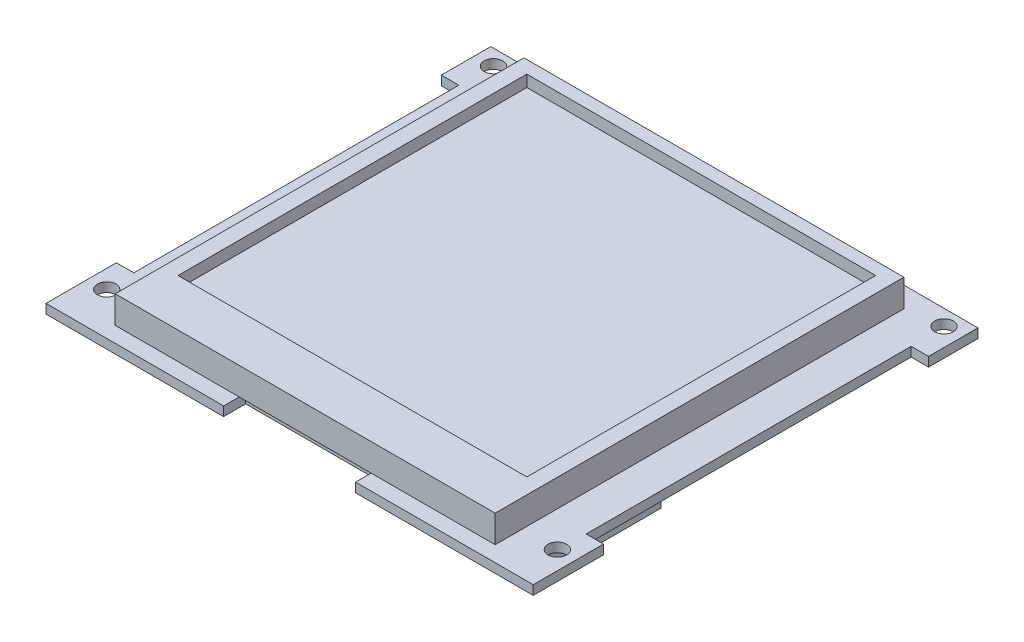
SolidWorks part; units mm, degrees
other "PCB"
other "显示屏"
ref_plane "前视基准面" through (0, 0, 0) normal (0, 0, 1) x (1, 0, 0)
ref_plane "上视基准面" through (0, 0, 0) normal (0, 1, 0) x (1, 0, 0)
ref_plane "右视基准面" through (0, 0, 0) normal (1, 0, 0) x (0, 0, -1)
other "Configuration Table"
sketch "草图1" plane through (0, 0, 0) normal (0, 1, 0) x (1, 0, 0)
  line L1 (-30, 70.8) -> (30, 70.8)
  line L2 (-30, 70.8) -> (-30, 10.8)
  line L3 (-30, 10.8) -> (30, 10.8)
  line L4 (30, 70.8) -> (30, 10.8)
  line L5 (-32.675, 72.98) -> (32.675, 72.98)
  line L6 (-32.675, 72.98) -> (-32.675, 2.68)
  line L7 (-32.675, 2.68) -> (32.675, 2.68)
  line L8 (32.675, 72.98) -> (32.675, 2.68)
  line L9 (-38.75, 73.8) -> (38.75, 73.8) construction
  line L10 (-38.75, 73.8) -> (-38.75, 7.3) construction
  line L11 (-38.75, 7.3) -> (38.75, 7.3) construction
  line L12 (38.75, 73.8) -> (38.75, 7.3) construction
  line L28 (-41.9, 76.5) -> (-41.9, 68)
  line L29 (-41.9, 68) -> (-38.9, 68)
  line L30 (-38.9, 68) -> (-38.9, 12.1)
  line L31 (-38.9, 12.1) -> (-41.9, 12.1)
  line L32 (-41.9, 12.1) -> (-41.9, 0)
  line L33 (0, 76.5) -> (0, 3.8) construction
  line L34 (-41.9, 0) -> (-11.35, 0)
  line L35 (-11.35, 0) -> (-11.35, 3.8)
  line L36 (11.35, 0) -> (11.35, 3.8)
  line L37 (41.9, 0) -> (11.35, 0)
  line L38 (41.9, 12.1) -> (41.9, 0)
  line L39 (38.9, 12.1) -> (41.9, 12.1)
  line L40 (38.9, 68) -> (38.9, 12.1)
  line L41 (41.9, 68) -> (38.9, 68)
  line L42 (41.9, 76.5) -> (41.9, 68)
  line L43 (-41.9, 76.5) -> (41.9, 76.5)
  line L44 (-11.35, 3.8) -> (11.35, 3.8)
  circle A0 centre (-38.75, 73.8) radius 1.6
  circle A1 centre (38.75, 73.8) radius 1.6
  circle A2 centre (38.75, 7.3) radius 1.6
  circle A3 centre (-38.75, 7.3) radius 1.6
  point P6 (0, 73.8)
  point P11 (0, 70.8)
  point P12 (0, 72.98)
  point P39 (0, 76.5)
  point P40 (0, 3.8)
  dimension "D7" = 3.2
  dimension "D1" = 60
  dimension "D2" = 60
  dimension "D3" = 65.35
  dimension "D4" = 70.3
  dimension "D5" = 77.5
  dimension "D6" = 66.5
  dimension "D8" = 83.8
  dimension "D9" = 8.5
  dimension "D10" = 55.9
  dimension "D11" = 12.1
  dimension "D12" = 3
  dimension "D13" = 22.7
  dimension "D14" = 3.8
  dimension "D15" = 2.68
  dimension "D16" = 7.3
  dimension "D17" = 10.8
extrude "凸台-拉伸1" add sketch "草图1" along normal blind 1.6 contours L34 L35 L44 L36 L37 L38 L39 L40 L41 L42 L43 L28 L29 L30 L31 L32 | A3 | A0 | A1 | A2
extrude "凸台-拉伸2" add sketch "草图1<3>" along normal blind 4.7 from surface separate body contours L6 L7 L8 L5 starting at face at (38.75, 1.6, -72.2)
sketch "草图1<3>" plane through (0, 0, 0) normal (0, 1, 0) x (1, 0, 0) same geometry as "草图1"
extrude "切除-拉伸1" cut sketch "草图1<4>" against normal blind 2 from surface contours L2 L3 L4 L1 starting at face at (0, 6.3, -37.83)
sketch "草图1<4>" plane through (0, 0, 0) normal (0, 1, 0) x (1, 0, 0) same geometry as "草图1"
sketch "草图2" plane through (0, 0, 0) normal (0, -1, 0) x (1, 0, 0)
  line L0 (41.9, -12.1) -> (41.9, 0) construction
  line L1 (30.9, -32.99) -> (25.9, -32.99)
  line L2 (30.9, -32.99) -> (30.9, -9.73)
  line L3 (30.9, -9.73) -> (25.9, -9.73)
  line L4 (25.9, -32.99) -> (25.9, -9.73)
  line L5 (32.05, -14.04) -> (32.05, -13.44)
  line L6 (28.4, -32.99) -> (28.4, -9.73) construction
  line L7 (32.05, -11.5) -> (30.9, -11.5)
  line L8 (32.05, -11.5) -> (32.05, -10.9)
  line L9 (32.05, -10.9) -> (30.9, -10.9)
  line L10 (30.9, -11.5) -> (30.9, -10.9)
  line L11 (32.05, -14.04) -> (30.9, -14.04)
  line L12 (30.9, -14.04) -> (30.9, -13.44)
  line L13 (32.05, -13.44) -> (30.9, -13.44)
  line L14 (32.05, -16.58) -> (32.05, -15.98)
  line L15 (32.05, -16.58) -> (30.9, -16.58)
  line L16 (30.9, -16.58) -> (30.9, -15.98)
  line L17 (32.05, -15.98) -> (30.9, -15.98)
  line L18 (32.05, -19.12) -> (32.05, -18.52)
  line L19 (32.05, -19.12) -> (30.9, -19.12)
  line L20 (30.9, -19.12) -> (30.9, -18.52)
  line L21 (32.05, -18.52) -> (30.9, -18.52)
  line L22 (32.05, -21.66) -> (32.05, -21.06)
  line L23 (32.05, -21.66) -> (30.9, -21.66)
  line L24 (30.9, -21.66) -> (30.9, -21.06)
  line L25 (32.05, -21.06) -> (30.9, -21.06)
  line L26 (32.05, -24.2) -> (32.05, -23.6)
  line L27 (32.05, -24.2) -> (30.9, -24.2)
  line L28 (30.9, -24.2) -> (30.9, -23.6)
  line L29 (32.05, -23.6) -> (30.9, -23.6)
  line L30 (32.05, -26.74) -> (32.05, -26.14)
  line L31 (32.05, -26.74) -> (30.9, -26.74)
  line L32 (30.9, -26.74) -> (30.9, -26.14)
  line L33 (32.05, -26.14) -> (30.9, -26.14)
  line L34 (32.05, -29.28) -> (32.05, -28.68)
  line L35 (32.05, -29.28) -> (30.9, -29.28)
  line L36 (30.9, -29.28) -> (30.9, -28.68)
  line L37 (32.05, -28.68) -> (30.9, -28.68)
  line L38 (32.05, -31.82) -> (32.05, -31.22)
  line L39 (32.05, -31.82) -> (30.9, -31.82)
  line L40 (30.9, -31.82) -> (30.9, -31.22)
  line L41 (32.05, -31.22) -> (30.9, -31.22)
  line L42 (32.05, -11.5) -> (32.05, -14.04) construction
  line L43 (24.75, -31.82) -> (25.9, -31.82)
  line L44 (25.9, -31.82) -> (25.9, -31.22)
  line L45 (24.75, -31.22) -> (25.9, -31.22)
  line L46 (24.75, -31.82) -> (24.75, -31.22)
  line L47 (24.75, -29.28) -> (25.9, -29.28)
  line L48 (25.9, -29.28) -> (25.9, -28.68)
  line L49 (24.75, -28.68) -> (25.9, -28.68)
  line L50 (24.75, -29.28) -> (24.75, -28.68)
  line L51 (24.75, -26.74) -> (25.9, -26.74)
  line L52 (25.9, -26.74) -> (25.9, -26.14)
  line L53 (24.75, -26.14) -> (25.9, -26.14)
  line L54 (24.75, -26.74) -> (24.75, -26.14)
  line L55 (24.75, -24.2) -> (25.9, -24.2)
  line L56 (25.9, -24.2) -> (25.9, -23.6)
  line L57 (24.75, -23.6) -> (25.9, -23.6)
  line L58 (24.75, -24.2) -> (24.75, -23.6)
  line L59 (24.75, -21.66) -> (25.9, -21.66)
  line L60 (25.9, -21.66) -> (25.9, -21.06)
  line L61 (24.75, -21.06) -> (25.9, -21.06)
  line L62 (24.75, -21.66) -> (24.75, -21.06)
  line L63 (24.75, -19.12) -> (25.9, -19.12)
  line L64 (25.9, -19.12) -> (25.9, -18.52)
  line L65 (24.75, -18.52) -> (25.9, -18.52)
  line L66 (24.75, -19.12) -> (24.75, -18.52)
  line L67 (24.75, -16.58) -> (25.9, -16.58)
  line L68 (25.9, -16.58) -> (25.9, -15.98)
  line L69 (24.75, -15.98) -> (25.9, -15.98)
  line L70 (24.75, -16.58) -> (24.75, -15.98)
  line L71 (24.75, -14.04) -> (25.9, -14.04)
  line L72 (25.9, -14.04) -> (25.9, -13.44)
  line L73 (24.75, -13.44) -> (25.9, -13.44)
  line L74 (24.75, -14.04) -> (24.75, -13.44)
  line L75 (24.75, -10.9) -> (25.9, -10.9)
  line L76 (25.9, -11.5) -> (25.9, -10.9)
  line L77 (24.75, -11.5) -> (25.9, -11.5)
  line L78 (24.75, -11.5) -> (24.75, -10.9)
  line L79 (24.75, -10.9) -> (24.75, -9.73) construction
  line L80 (24.75, -31.82) -> (24.75, -32.99) construction
  line L81 (41.9, 0) -> (11.35, 0) construction
  line L82 (30.42, -11.95) -> (28.92, -11.95)
  line L83 (26.38, -10.45) -> (27.88, -10.45)
  line L84 (26.38, -10.45) -> (26.38, -11.95)
  line L85 (26.38, -11.95) -> (27.88, -11.95)
  line L86 (27.88, -10.45) -> (27.88, -11.95)
  line L87 (28.92, -10.45) -> (28.92, -11.95)
  line L88 (30.42, -10.45) -> (28.92, -10.45)
  line L89 (30.42, -10.45) -> (30.42, -11.95)
  line L90 (26.38, -12.99) -> (26.38, -14.49)
  line L91 (26.38, -12.99) -> (27.88, -12.99)
  line L92 (27.88, -12.99) -> (27.88, -14.49)
  line L93 (26.38, -14.49) -> (27.88, -14.49)
  line L94 (30.42, -14.49) -> (28.92, -14.49)
  line L95 (28.92, -12.99) -> (28.92, -14.49)
  line L96 (30.42, -12.99) -> (28.92, -12.99)
  line L97 (30.42, -12.99) -> (30.42, -14.49)
  line L98 (26.38, -15.53) -> (26.38, -17.03)
  line L99 (26.38, -15.53) -> (27.88, -15.53)
  line L100 (27.88, -15.53) -> (27.88, -17.03)
  line L101 (26.38, -17.03) -> (27.88, -17.03)
  line L102 (30.42, -17.03) -> (28.92, -17.03)
  line L103 (28.92, -15.53) -> (28.92, -17.03)
  line L104 (30.42, -15.53) -> (28.92, -15.53)
  line L105 (30.42, -15.53) -> (30.42, -17.03)
  line L106 (26.38, -18.07) -> (26.38, -19.57)
  line L107 (26.38, -18.07) -> (27.88, -18.07)
  line L108 (27.88, -18.07) -> (27.88, -19.57)
  line L109 (26.38, -19.57) -> (27.88, -19.57)
  line L110 (30.42, -19.57) -> (28.92, -19.57)
  line L111 (28.92, -18.07) -> (28.92, -19.57)
  line L112 (30.42, -18.07) -> (28.92, -18.07)
  line L113 (30.42, -18.07) -> (30.42, -19.57)
  line L114 (26.38, -20.61) -> (26.38, -22.11)
  line L115 (26.38, -20.61) -> (27.88, -20.61)
  line L116 (27.88, -20.61) -> (27.88, -22.11)
  line L117 (26.38, -22.11) -> (27.88, -22.11)
  line L118 (30.42, -22.11) -> (28.92, -22.11)
  line L119 (28.92, -20.61) -> (28.92, -22.11)
  line L120 (30.42, -20.61) -> (28.92, -20.61)
  line L121 (30.42, -20.61) -> (30.42, -22.11)
  line L122 (26.38, -23.15) -> (26.38, -24.65)
  line L123 (26.38, -23.15) -> (27.88, -23.15)
  line L124 (27.88, -23.15) -> (27.88, -24.65)
  line L125 (26.38, -24.65) -> (27.88, -24.65)
  line L126 (30.42, -24.65) -> (28.92, -24.65)
  line L127 (28.92, -23.15) -> (28.92, -24.65)
  line L128 (30.42, -23.15) -> (28.92, -23.15)
  line L129 (30.42, -23.15) -> (30.42, -24.65)
  line L130 (26.38, -25.69) -> (26.38, -27.19)
  line L131 (26.38, -25.69) -> (27.88, -25.69)
  line L132 (27.88, -25.69) -> (27.88, -27.19)
  line L133 (26.38, -27.19) -> (27.88, -27.19)
  line L134 (30.42, -27.19) -> (28.92, -27.19)
  line L135 (28.92, -25.69) -> (28.92, -27.19)
  line L136 (30.42, -25.69) -> (28.92, -25.69)
  line L137 (30.42, -25.69) -> (30.42, -27.19)
  line L138 (26.38, -28.23) -> (26.38, -29.73)
  line L139 (26.38, -28.23) -> (27.88, -28.23)
  line L140 (27.88, -28.23) -> (27.88, -29.73)
  line L141 (26.38, -29.73) -> (27.88, -29.73)
  line L142 (30.42, -29.73) -> (28.92, -29.73)
  line L143 (28.92, -28.23) -> (28.92, -29.73)
  line L144 (30.42, -28.23) -> (28.92, -28.23)
  line L145 (30.42, -28.23) -> (30.42, -29.73)
  line L146 (26.38, -30.77) -> (26.38, -32.27)
  line L147 (26.38, -30.77) -> (27.88, -30.77)
  line L148 (27.88, -30.77) -> (27.88, -32.27)
  line L149 (26.38, -32.27) -> (27.88, -32.27)
  line L150 (30.42, -32.27) -> (28.92, -32.27)
  line L151 (28.92, -30.77) -> (28.92, -32.27)
  line L152 (30.42, -30.77) -> (28.92, -30.77)
  line L153 (30.42, -30.77) -> (30.42, -32.27)
  line L154 (26.38, -10.45) -> (26.38, -12.99) construction
  point P91 (32.05, -11.2)
  point P96 (24.75, -11.2)
  point P97 (26.38, -11.2)
  point P164 (27.13, -10.45)
  point P165 (29.67, -10.45)
  dimension "D1" = 23.26
  dimension "D2" = 5
  dimension "D3" = 13.5
  dimension "D4" = 0.6
  dimension "D6" = 2.54
  dimension "D7" = 7.3
  dimension "D8" = 11.2
  dimension "D10" = 2.54
  dimension "D11" = 2.54
  dimension "D12" = 1.5
  dimension "D5" = 9
  dimension "D9" = 9
extrude "凸台-拉伸3" add sketch "草图2" along normal blind 9 separate body contours L3 L4 L1 L2
extrude "凸台-拉伸4" add sketch "草图2<3>" along normal blind 0.5 contours L9 L10 L7 L8 | L13 L12 L11 L5 | L17 L16 L15 L14 | L41 L40 L39 L38 | L37 L36 L35 L34 | L33 L32 L31 L30 | L27 L28 L29 L26 | L23 L24 L25 L22 | L21 L20 L19 L18 | L45 L44 L43 L46 | L49 L48 L47 L50 | L53 L52 L51 L54 | L57 L56 L55 L58 | L61 L60 L59 L62 | L65 L64 L63 L66 | L67 L68 L69 L70 | L71 L72 L73 L74 | L75 L76 L77 L78
sketch "草图2<3>" plane through (0, 0, 0) normal (0, -1, 0) x (1, 0, 0) same geometry as "草图2"
extrude "切除-拉伸2" cut sketch "草图2<4>" against normal blind 5 from surface contours L151 L150 L153 L152 | L148 L149 L146 L147 | L143 L142 L145 L144 | L140 L141 L138 L139 | L135 L134 L137 L136 | L132 L133 L130 L131 | L127 L126 L129 L128 | L124 L125 L122 L123 | L119 L118 L121 L120 | L116 L117 L114 L115 | L111 L110 L113 L112 | L108 L109 L106 L107 | L103 L102 L105 L104 | L100 L101 L98 L99 | L95 L94 L97 L96 | L92 L93 L90 L91 | L87 L82 L89 L88 | L86 L85 L84 L83 starting at face at (28.4, -9, -21.36)
sketch "草图2<4>" plane through (0, 0, 0) normal (0, -1, 0) x (1, 0, 0) same geometry as "草图2"
